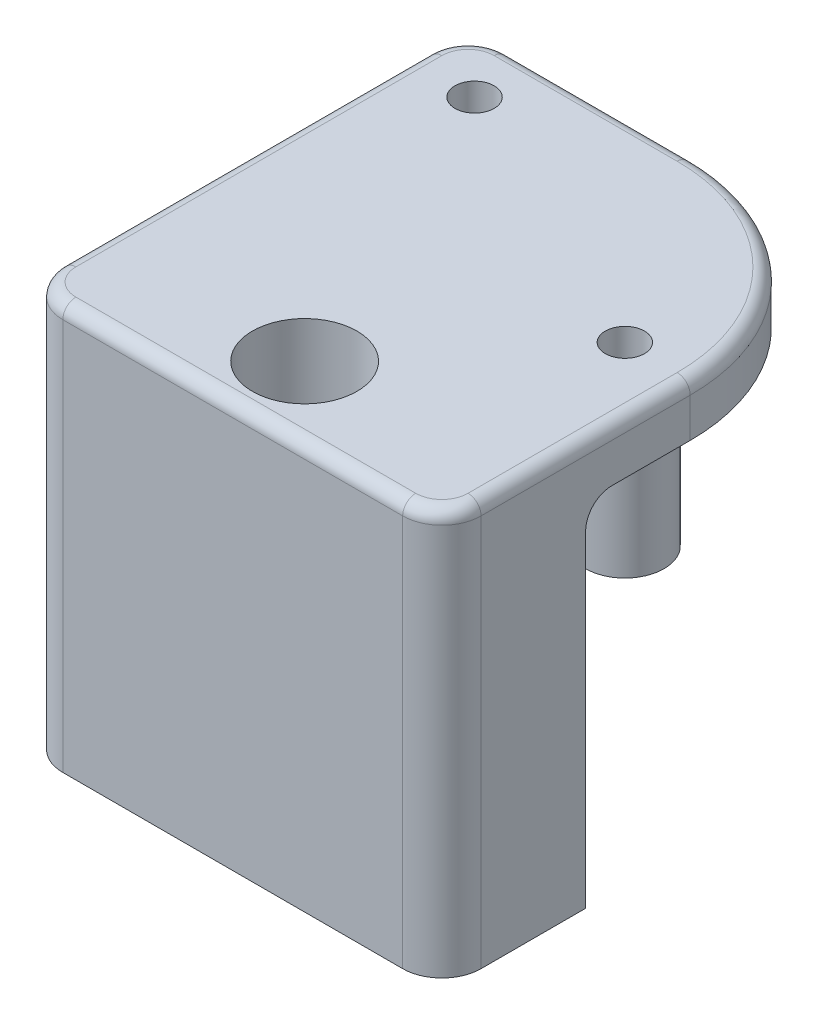
SolidWorks part; units mm, degrees
ref_plane "Спереди" through (0, 0, 0) normal (0, 0, 1) x (1, 0, 0)
ref_plane "Сверху" through (0, 0, 0) normal (0, 1, 0) x (1, 0, 0)
ref_plane "Справа" through (0, 0, 0) normal (1, 0, 0) x (0, 0, -1)
sketch "Эскиз1" plane through (0, 0, 0) normal (0, 1, 0) x (1, 0, 0)
  line L0 (0, 5.5) -> (32, 5.5) construction
  line L1 (0, 0) -> (32, 0)
  line L2 (0, 0) -> (0, 11)
  line L3 (0, 11) -> (32, 11)
  line L4 (32, 0) -> (32, 11)
  line L5 (16, 11) -> (16, 0) construction
  circle A0 centre (16, 5.5) radius 1.6
  dimension "D3" = 3.2
  dimension "D1" = 11
  dimension "D2" = 32
extrude "Бобышка-Вытянуть1" add sketch "Эскиз1" along normal blind 27
sketch "Эскиз2" plane through (0, 27, 0) normal (0, 1, 0) x (1, 0, 0)
  line L0 (32, 0) -> (32, 11) construction
  line L4 (32, 0) -> (32, 19)
  line L5 (32, 0) -> (0, 0)
  line L7 (17, 34) -> (3, 34)
  line L8 (0, 0) -> (0, 31)
  circle A0 centre (5, 29.5) radius 1.5
  circle A1 centre (27, 19) radius 1.5
  arc A2 (17, 34) -> (32, 19) centre (17, 19) cw
  arc A3 (3, 34) -> (0, 31) centre (3, 31) ccw
  point P15 (32, 34)
  point P18 (0, 34)
  dimension "D6" = 3
  dimension "D7" = 3
  dimension "D8" = 5
  dimension "D9" = 5
  dimension "D10" = 15
  dimension "D5" = 29.5
  dimension "D11" = 19
  dimension "D2" = 32
  dimension "D3" = 34
  dimension "D4" = 0
extrude "Бобышка-Вытянуть2" add sketch "Эскиз2" along normal blind 4
fillet "Скругление3" radius 3 1 edges at (32, 15.5, 0) tangent propagation no
fillet "Скругление4" radius 3 1 edges at (0, 15.5, 0) tangent propagation no
sketch "Эскиз3" plane through (0, 27, 0) normal (0, -1, 0) x (1, 0, 0)
  circle A0 centre (16, -5.5) radius 4
  dimension "D1" = 8
extrude "Вырез-Вытянуть1" cut sketch "Эскиз3" against normal blind 15 from offset 10
fillet "Скругление5" radius 2 1 edges at (16, 27, -11)
sketch "Эскиз4" plane through (0, 27, 0) normal (0, -1, 0) x (1, 0, 0)
  circle A0 centre (27, -19) radius 1.5
  circle A1 centre (27, -19) radius 3
  dimension "D1" = 6
extrude "Бобышка-Вытянуть3" add sketch "Эскиз4" along normal blind 9.5
fillet "Скругление6" radius 1 8 edges at (32, 31, -11) (27.6066, 31, -29.6066) (10, 31, -34) (0.8787, 31, -33.1213) (0, 31, -17) (31.1213, 31, -0.8787) (16, 31, 0) (0.8787, 31, -0.8787)
